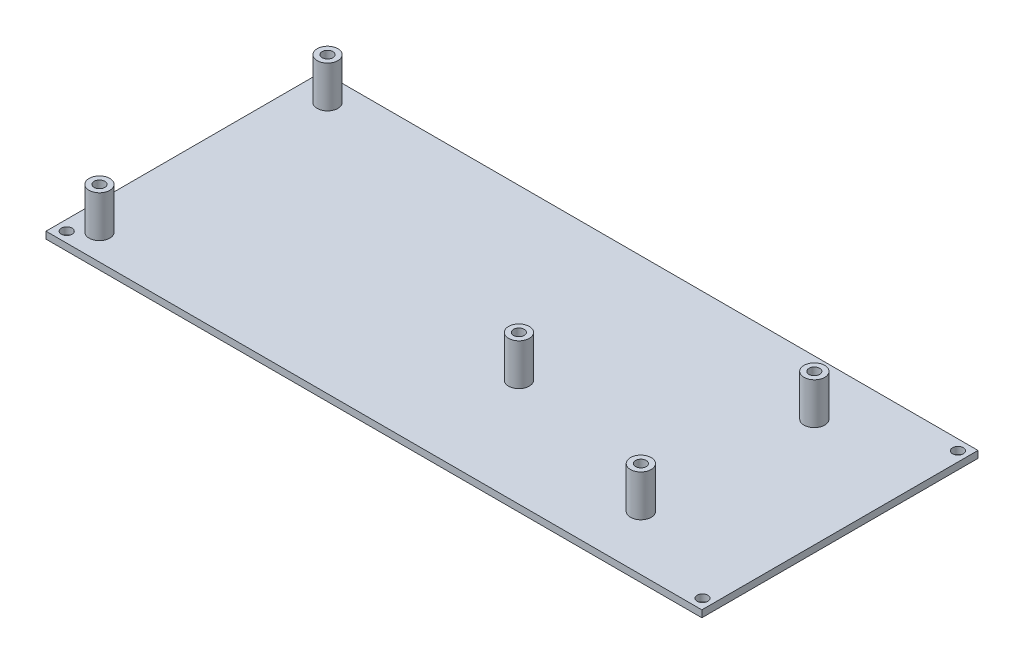
SolidWorks part; units mm, degrees
ref_plane "Front Plane" through (0, 0, 0) normal (0, 0, 1) x (1, 0, 0)
ref_plane "Top Plane" through (0, 0, 0) normal (0, 1, 0) x (1, 0, 0)
ref_plane "Right Plane" through (0, 0, 0) normal (1, 0, 0) x (0, 0, -1)
sketch "Sketch1" plane through (0, 0, 0) normal (0, 1, 0) x (1, 0, 0)
  line L1 (-75.7488, 40.5797) -> (114.2512, 40.5797)
  line L2 (-75.7488, 40.5797) -> (-75.7488, -39.4203)
  line L3 (-75.7488, -39.4203) -> (114.2512, -39.4203)
  line L4 (114.2512, 40.5797) -> (114.2512, -39.4203)
  circle A0 centre (-72.7488, 37.5797) radius 1.55
  circle A1 centre (111.4359, 37.5797) radius 1.55
  circle A2 centre (111.4359, -36.4203) radius 1.55
  circle A3 centre (-72.7488, -36.4203) radius 1.55
  dimension "D3" = 3.1
  dimension "D1" = 80
  dimension "D2" = 190
  dimension "D4" = 3
  dimension "D5" = 3
  dimension "D6" = 3
extrude "Boss-Extrude1" add sketch "Sketch1" along normal blind 2
sketch "Sketch2" plane through (0, 2, 0) normal (0, 1, 0) x (1, 0, 0)
  line L0 (-75.7488, 40.5797) -> (-75.7488, -39.4203) construction
  line L1 (27.7512, 35.5797) -> (110.2512, 35.5797) construction
  line L2 (27.7512, 35.5797) -> (27.7512, -34.4203) construction
  line L3 (27.7512, -34.4203) -> (110.2512, -34.4203) construction
  line L4 (110.2512, 35.5797) -> (110.2512, -34.4203) construction
  line L5 (-71.7488, 37.2097) -> (20.0912, 37.2097) construction
  line L6 (-71.7488, 37.2097) -> (-71.7488, -36.0503) construction
  line L7 (-71.7488, -36.0503) -> (20.0912, -36.0503) construction
  line L8 (-98.3486, 0.5797) -> (132.2607, 0.5797) construction
  line L9 (114.2512, 40.5797) -> (-75.7488, 40.5797) construction
  line L10 (-75.7488, -39.4203) -> (114.2512, -39.4203) construction
  line L11 (114.2512, -39.4203) -> (114.2512, 40.5797) construction
  line L12 (20.0912, 37.2097) -> (20.0912, -36.0503) construction
  circle A0 centre (82.7112, 24.7097) radius 3
  circle A1 centre (80.7112, -23.5503) radius 3
  circle A2 centre (30.1412, -8.3103) radius 3
  circle A3 centre (82.7112, 24.7097) radius 1.55
  circle A4 centre (80.7112, -23.5503) radius 1.55
  circle A5 centre (30.1412, -8.3103) radius 1.55
  circle A6 centre (-67.2588, 33.6497) radius 3
  circle A7 centre (-67.7488, -31.9303) radius 3
  circle A8 centre (-67.2588, 33.6497) radius 1.55
  circle A9 centre (-67.7488, -31.9303) radius 1.55
  dimension "D4" = 6
  dimension "D11" = 3.1
  dimension "D1" = 70
  dimension "D2" = 82.5
  dimension "D3" = 4
  dimension "D5" = 27.54
  dimension "D6" = 10.87
  dimension "D7" = 29.54
  dimension "D8" = 10.87
  dimension "D9" = 2.39
  dimension "D10" = 33.02
  dimension "D12" = 73.26
  dimension "D13" = 91.84
  dimension "D14" = 4
  dimension "D15" = 3.56
  dimension "D16" = 4.49
  dimension "D17" = 4.12
  dimension "D18" = 4
extrude "Boss-Extrude2" add sketch "Sketch2" along normal blind 12
